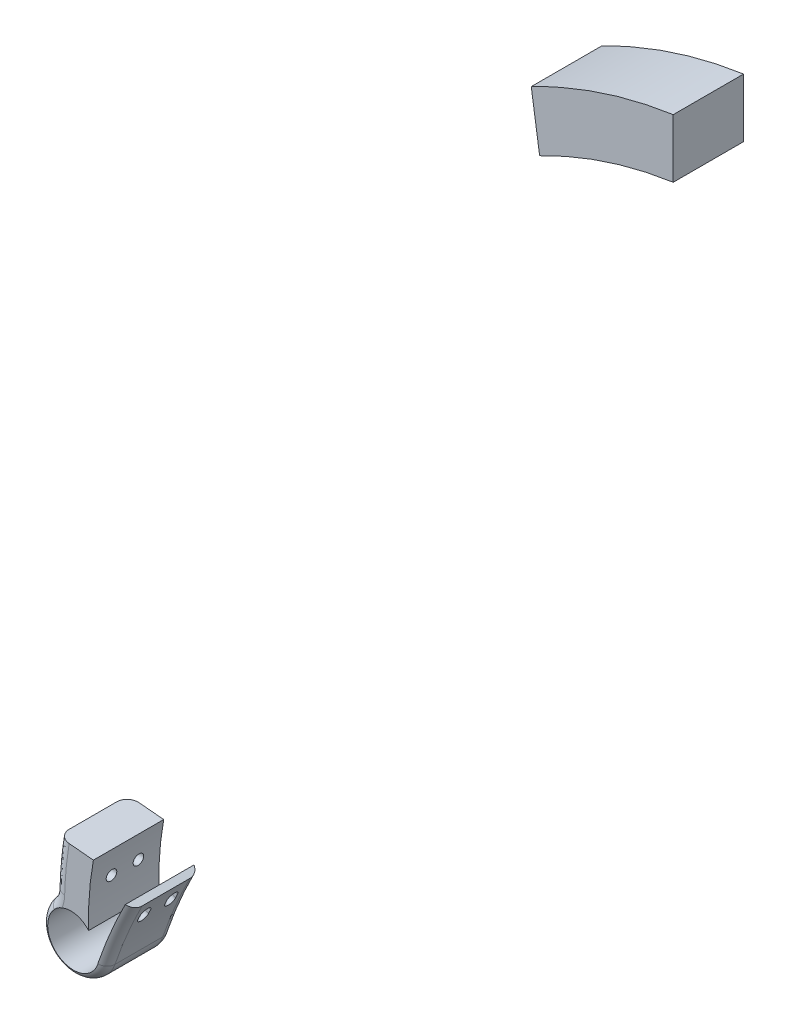
SolidWorks part; units mm, degrees
material "ABS"
ref_plane "Front Plane" through (0, 0, 0) normal (0, 0, 1) x (1, 0, 0)
ref_plane "Top Plane" through (0, 0, 0) normal (0, 1, 0) x (1, 0, 0)
ref_plane "Right Plane" through (0, 0, 0) normal (1, 0, 0) x (0, 0, -1)
sketch "Sketch1" plane through (0, 0, 0) normal (0, 0, 1) x (1, 0, 0)
  line L0 (-307.5, -289.3816) -> (-292.5, -289.3816) construction
  line L1 (-313, -300) -> (-318, -300) construction
  line L2 (-318, -318) -> (-43, -318) construction
  line L3 (-318, -318) -> (-318, -78) construction
  line L4 (-318, -78) -> (-43, -78) construction
  line L5 (-43, -318) -> (-43, -78) construction
  line L6 (-318, -318) -> (-43, -78) construction
  line L7 (-318, -78) -> (-43, -318) construction
  line L8 (-300, -313) -> (-300, -318) construction
  circle A0 centre (-300, -300) radius 10
  circle A1 centre (0, 0) radius 150 construction
  circle A2 centre (-300, -300) radius 13
  ellipse E0 centre (-43, -289.3816) end of major axis (-300, -289.3816) minor radius 189.3816 construction
  ellipse E1 centre (-43, -289.3816) end of major axis (-307.5, -289.3816) minor radius 201.3816 (-43, -88) -> (-307.5, -289.3816) ccw
  ellipse E2 centre (-43, -289.3816) end of major axis (-292.5, -289.3816) minor radius 177.3816 (-292.5, -289.3816) -> (-43, -112) cw
  point P15 (-180.5, -198)
  point P43 (-299.9797, -287)
  dimension "D2" = 20
  dimension "D3" = 300
  dimension "D5" = 100
  dimension "D6" = 26
  dimension "D9" = 5
  dimension "D1" = 300
  dimension "D4" = 300
  dimension "D7" = 275
  dimension "D8" = 240
  dimension "D10" = 15
  dimension "D11" = 12
  dimension "D12" = 12
  dimension "D13" = 257
sketch "Sketch2" plane through (0, 0, 0) normal (0, 0, 1) x (1, 0, 0)
  line L0 (-43, -289.3816) -> (-306.971, -276.6512) construction
  line L1 (-292.434, -293.4612) -> (-307.566, -293.4612) construction
  line L2 (-292.4554, -292.7993) -> (-292.9764, -276.6978) construction
  line L3 (-306.7301, -271.657) -> (-291.8265, -272.3758) construction
  line L4 (-306.7301, -271.657) -> (-307.2118, -281.6454) construction
  line L5 (-307.2118, -281.6454) -> (-292.3082, -282.3642) construction
  line L6 (-291.8265, -272.3758) -> (-292.3082, -282.3642) construction
  line L7 (-306.7301, -271.657) -> (-292.3082, -282.3642) construction
  line L8 (-307.2118, -281.6454) -> (-291.8265, -272.3758) construction
  line L9 (-292.434, -293.4612) -> (-299.2434, -300.6539) construction
  line L10 (-299.2434, -300.6539) -> (-288.5443, -303.2091) construction
  line L11 (-307.566, -293.4612) -> (-300, -300) construction
  line L12 (-300, -300) -> (-290.0814, -298.7264) construction
  line L13 (-290.0814, -298.7264) -> (-290.7705, -277.4325) construction
  line L14 (-288.5443, -303.2091) -> (-277.3623, -270.5344) construction
  line L15 (-43, -289.3816) -> (-290.919, -269.4442) construction
  line L16 (-274.4361, -277.7752) -> (-277.1478, -276.3849)
  line L17 (-96.9466, -368.7781) -> (-274.4361, -277.7752) construction
  line L19 (-96.9466, -368.7781) -> (-277.9411, -284.9625) construction
  line L20 (-290.919, -269.4442) -> (-291.9279, -277.3767) construction
  line L21 (-274.4361, -277.7752) -> (-277.9411, -284.9625) construction
  line L22 (-305.5543, -265) -> (-290.3985, -266.4074)
  line L23 (-290.3985, -266.4074) -> (-43, -289.3816) construction
  line L25 (-43, -289.3816) -> (-112.832, 107.7448) construction
  line L26 (-43, -289.3816) -> (-303.1687, -243.1326) construction
  line L30 (-43, -289.3816) -> (-43, 107.7448) construction
  line L31 (-290.3985, -266.4074) -> (-286.7789, -246.0461) construction
  line L32 (-299.9797, -287) -> (-43, -289.3816) construction
  line L33 (-290.3985, -266.4074) -> (-290.5901, -287.087) construction
  line L34 (-43, -289.3816) -> (-103.577, 112.8172) construction
  line L36 (-43, 107.7448) -> (-43, 132.7448)
  line L37 (-103.577, 112.8172) -> (-100, 89.0681)
  circle A0 centre (-300, -300) radius 10 construction
  arc A1 (-292.434, -293.4612) -> (-307.566, -293.4612) centre (-300, -300) ccw
  arc A2 (-307.566, -293.4612) -> (-288.5443, -303.2091) centre (-299.2434, -300.6539) ccw
  arc A3 (-309.8358, -291.4996) -> (-285.9755, -305.1219) centre (-299.2434, -300.6539) ccw
  arc A4 (-309.8358, -291.4996) -> (-307.4465, -285.3313) centre (-317.2735, -285.0717) ccw
  arc A5 (-307.566, -293.4612) -> (-290.0814, -298.7264) centre (-300, -300) ccw construction
  arc A7 (-309.8358, -291.4996) -> (-285.6264, -303.906) centre (-299.2434, -300.6539) ccw construction
  arc A8 (-290.0814, -298.7264) -> (-288.9254, -269.6045) centre (-87.6806, -292.177) cw construction
  arc A9 (-288.5443, -303.2091) -> (-277.1478, -276.3849) centre (-96.9466, -368.7781) cw
  arc A10 (-285.9755, -305.1219) -> (-274.4361, -277.7752) centre (-96.9466, -368.7781) cw
  ellipse E1 centre (-43, -289.3816) end of major axis (-292.5, -289.3816) minor radius 177.3816 (-292.434, -293.4612) -> (-290.3985, -266.4074) cw
  ellipse E2 centre (-43, -289.3816) end of major axis (-307.5, -289.3816) minor radius 201.3816 (-43, -88) -> (-307.5, -289.3816) ccw construction
  ellipse E3 centre (-43, -289.3816) end of major axis (-79.9691, -687.4843) minor radius 248.4629 (-43, 107.7448) -> (-100, 89.0681) ccw
  ellipse E4 centre (-43, -289.3816) end of major axis (206.5, -289.3816) minor radius 177.3816 (-43, -112) -> (-292.5, -289.3816) ccw construction
  ellipse E5 centre (-43, -289.3816) end of major axis (-307.5, -289.3816) minor radius 201.3816 (-305.5543, -265) -> (-307.4465, -285.3313) ccw
  ellipse E6 centre (-43, -289.3816) end of major axis (-79.9691, -687.4843) minor radius 248.4629 (-288.1496, -245.8025) -> (-290.3985, -266.4074) ccw
  ellipse E7 centre (-43, -289.3816) end of major axis (-3.7022, 133.7976) minor radius 263.6839 (-43, 132.7448) -> (-103.577, 112.8172) ccw
  ellipse E8 centre (-43, -289.3816) end of major axis (-79.9691, -687.4843) minor radius 248.4629 (-100, 89.0681) -> (-288.1496, -245.8025) ccw
  ellipse E9 centre (-43, -289.3816) end of major axis (-4.8858, 121.0525) minor radius 256.0734 construction
  ellipse E10 centre (-43, -289.3816) end of major axis (-3.7022, 133.7976) minor radius 263.6839 (-103.577, 112.8172) -> (-305.5543, -265) ccw
  point P1 (-299.5192, -277.0106)
  point P66 (-297.9764, -265.7037)
  dimension "D1" = 5
  dimension "D3" = 11
  dimension "D7" = 95.464
  dimension "D11" = 202.5067
  dimension "D12" = 100
  dimension "D16" = 9.8304
  dimension "D2" = 10
  dimension "D4" = 60
  dimension "D6" = 228.152
  dimension "D8" = 95.46
  dimension "D9" = 2
  dimension "D10" = 20
  dimension "D13" = 35
  dimension "D14" = 25
  dimension "D15" = 4.8858
  dimension "D17" = 107.7448
  dimension "D20" = 204.3985
  dimension "D21" = 6.0309
  dimension "D5" = 3
extrude "Boss-Extrude1" add sketch "Sketch2" along normal blind 30
ref_plane "Plane1" through (-278.0441, 13.4091, 0) normal (-0.9988, 0.0482, 0) x (-0.0482, -0.9988, 0)
sketch "Sketch4" plane through (-278.0441, 13.4091, 0) normal (-0.9988, 0.0482, 0) x (-0.0482, -0.9988, 0)
  line L0 (291.117, 0) -> (291.117, 7) construction
  line L1 (291.117, 23) -> (291.117, 30) construction
  line L2 (291.117, 11.5) -> (291.117, 18.5) construction
  line L6 (279.4111, 0) -> (299.8099, 0) construction
  line L9 (299.8099, 0) -> (299.8099, 30) construction
  line L15 (299.8099, 30) -> (279.4111, 30) construction
  line L17 (279.4111, 30) -> (279.4111, 0) construction
  circle A0 centre (291.117, 20.75) radius 2.25
  circle A1 centre (291.117, 9.25) radius 2.25
  dimension "D2" = 4.5
  dimension "D3" = 30
  dimension "D1" = 279.4111
  dimension "D4" = 299.8099
  dimension "D5" = 9.25
extrude "Cut-Extrude1" cut sketch "Sketch4" along normal through all and the other way up to next
ref_plane "Plane2" through (-112.2757, 54.7524, 0) normal (-0.8988, 0.4383, 0) x (-0.4383, -0.8988, 0)
sketch "Sketch5" plane through (-112.2757, 54.7524, 0) normal (-0.8988, 0.4383, 0) x (-0.4383, -0.8988, 0)
  line L0 (376.9567, 20.75) -> (378.9567, 20.75) construction
  line L1 (376.9567, 23) -> (378.9567, 23)
  line L2 (376.9567, 18.5) -> (378.9567, 18.5)
  line L3 (376.9567, 9.25) -> (378.9567, 9.25) construction
  line L4 (376.9567, 11.5) -> (378.9567, 11.5)
  line L5 (376.9567, 7) -> (378.9567, 7)
  line L6 (377.9567, 30) -> (377.9567, 23) construction
  line L7 (377.9567, 18.5) -> (377.9567, 11.5) construction
  line L8 (377.9567, 7) -> (377.9567, 0) construction
  line L10 (369.9603, 0) -> (399.5979, 0)
  line L11 (369.9603, 30) -> (369.9603, 0)
  line L13 (399.5979, 0) -> (399.5979, 30)
  line L15 (369.9603, 30) -> (369.9603, 0) construction
  line L21 (399.5979, 30) -> (369.9603, 30)
  arc A0 (376.9567, 23) -> (376.9567, 18.5) centre (376.9567, 20.75) ccw
  arc A1 (378.9567, 18.5) -> (378.9567, 23) centre (378.9567, 20.75) ccw
  arc A2 (376.9567, 11.5) -> (376.9567, 7) centre (376.9567, 9.25) ccw
  arc A3 (378.9567, 7) -> (378.9567, 11.5) centre (378.9567, 9.25) ccw
  point P2 (377.9567, 20.75)
  point P7 (377.9567, 9.25)
  dimension "D2" = 4.5
  dimension "D3" = 2
  dimension "D1" = 0
extrude "Cut-Extrude2" cut sketch "Sketch5" along normal up to next and the other way through all
ref_plane "Plane3" through (-51.1835, -287.9269, 0) normal (0.175, 0.9846, 0) x (-0.9846, 0.175, 0)
fillet "Fillet3" radius 4.8 6 edges at (-280.7152, -291.2336, 0) (-280.7152, -291.2336, 30) (-308.1067, -288.6225, 0) (-308.1067, -288.6225, 30) (-306.8384, -275.1474, 0) (-306.8384, -275.1474, 30)
sketch "Sketch11" plane through (-278.0441, 13.4091, 0) normal (-0.9988, 0.0482, 0) x (-0.0482, -0.9988, 0)
  line L1 (291.117, 16.4199) -> (294.867, 18.5849)
  line L2 (294.867, 18.5849) -> (294.867, 22.9151)
  line L3 (294.867, 22.9151) -> (291.117, 25.0801)
  line L4 (291.117, 25.0801) -> (287.367, 22.9151)
  line L5 (287.367, 22.9151) -> (287.367, 18.5849)
  line L6 (287.367, 18.5849) -> (291.117, 16.4199)
  line L7 (294.867, 7.0849) -> (294.867, 11.4151)
  line L8 (294.867, 11.4151) -> (291.117, 13.5801)
  line L9 (291.117, 13.5801) -> (287.367, 11.4151)
  line L10 (287.367, 11.4151) -> (287.367, 7.0849)
  line L11 (287.367, 7.0849) -> (291.117, 4.9199)
  line L12 (291.117, 4.9199) -> (294.867, 7.0849)
  circle A0 centre (291.117, 20.75) radius 3.75 construction
  circle A1 centre (291.117, 9.25) radius 3.75 construction
  dimension "D1" = 7.5
extrude "Cut-Extrude5" cut sketch "Sketch11" along normal blind 14 from offset 11
